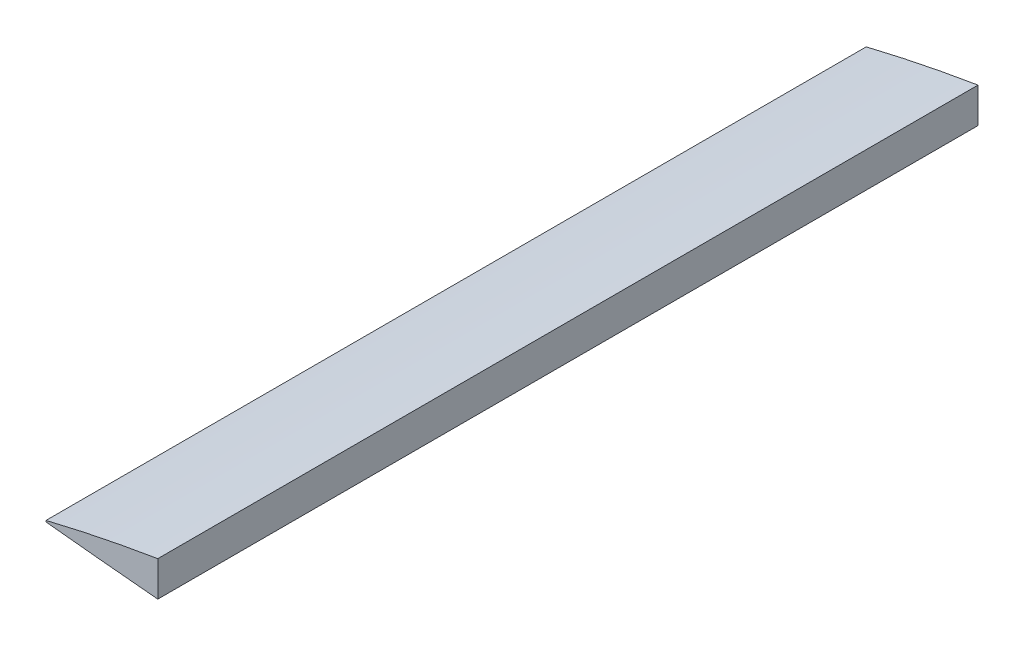
SolidWorks part; units mm, degrees
ref_plane "Front Plane" through (0, 0, 0) normal (0, 0, 1) x (1, 0, 0)
ref_plane "Top Plane" through (0, 0, 0) normal (0, 1, 0) x (1, 0, 0)
ref_plane "Right Plane" through (0, 0, 0) normal (1, 0, 0) x (0, 0, -1)
sketch "Sketch1" plane through (0, 0, 0) normal (0, 0, 1) x (1, 0, 0)
  line L0 (-237.3661, 17.5023) -> (-237.3661, -8.6743)
  line L1 (-320.765, 0.5123) -> (-320.765, -0.5041)
  spline S0 degree 3 poles (-237.3661, 17.5023) (-239.8019, 17.0983) (-245.7286, 16.1153) (-254.935, 14.4753) (-264.7764, 12.6474) (-273.9672, 10.8586) (-282.4535, 9.1393) (-290.1848, 7.5144) (-297.1155, 6.0094) (-303.2051, 4.6483) (-308.4182, 3.4537) (-312.7248, 2.4459) (-316.1, 1.6425) (-318.5247, 1.0579) (-319.9739, 0.7056) (-320.6133, 0.5494) (-320.765, 0.5123) knots 0 0 0 0 0.087007 0.211705 0.329527 0.439741 0.541661 0.634652 0.718135 0.791585 0.85454 0.906603 0.947445 0.976805 0.994497 1 1 1 1
  spline S1 degree 3 poles (-237.3661, -8.6743) (-239.4751, -8.4831) (-245.0808, -7.9749) (-253.9919, -7.1469) (-263.889, -6.2146) (-273.1542, -5.3269) (-281.7285, -4.4926) (-289.557, -3.719) (-296.5894, -3.0139) (-302.7801, -2.3837) (-308.0889, -1.8378) (-312.4807, -1.376) (-315.9277, -1.0227) (-318.4047, -0.7374) (-319.9003, -0.617) (-320.5749, -0.5034) (-320.7538, -0.504) (-320.765, -0.5041) knots 0 0 0 0 0.075811 0.201508 0.320388 0.431695 0.534719 0.628797 0.713321 0.78774 0.851567 0.90438 0.945827 0.975633 0.993597 0.999599 1 1 1 1
extrude "Boss-Extrude1" add sketch "Sketch1" against normal blind 612
ref_plane "Plane1" through (0, 0, -96.9) normal (0, 0, 1) x (1, 0, 0)
sketch "Sketch2" plane through (0, 0, -96.9) normal (0, 0, 1) x (1, 0, 0)
  line L0 (-261.074, -9.053) -> (-240.074, -9.053)
  line L1 (-240.074, -9.053) -> (-240.074, 2.447)
  line L2 (-240.074, 2.447) -> (-261.074, 2.447)
  line L3 (-261.074, 2.447) -> (-261.074, -9.053)
extrude "Cut-Extrude1" cut sketch "Sketch2" along normal blind 13
